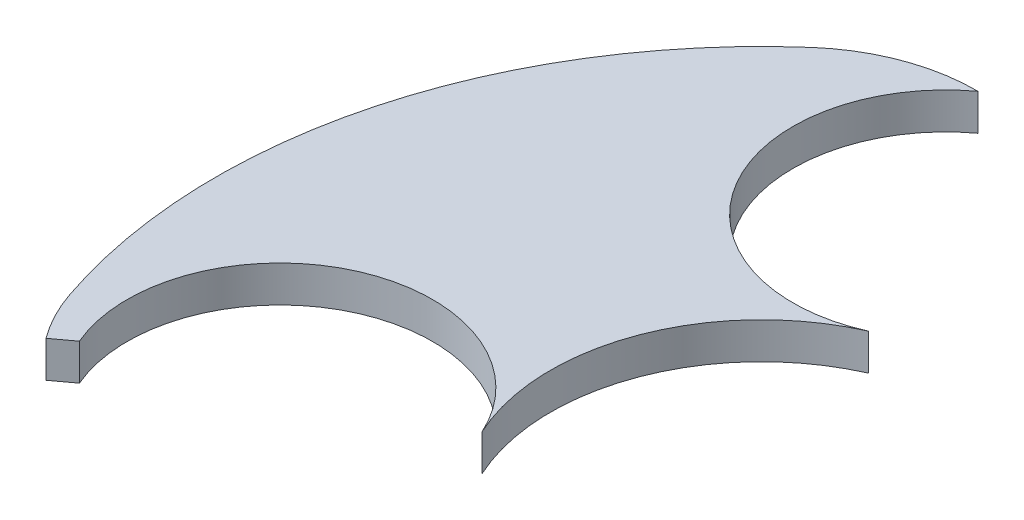
SolidWorks part; units mm, degrees
ref_plane "Plan de face" through (0, 0, 0) normal (0, 0, 1) x (1, 0, 0)
ref_plane "Plan de dessus" through (0, 0, 0) normal (0, 1, 0) x (1, 0, 0)
ref_plane "Plan de droite" through (0, 0, 0) normal (1, 0, 0) x (0, 0, -1)
sketch "Esquisse1" plane through (0, 0, 0) normal (0, 1, 0) x (1, 0, 0)
  line L0 (-84.4585, -44.8337) -> (-81.8158, -42.8843)
  line L3 (-9.4508, 5.6286) -> (-14.9085, -3.5351) construction
  line L5 (3.3105, -15.9387) -> (9.4508, -5.6286) construction
  line L12 (0, 0) -> (-80, 0) construction
  line L13 (-64.3402, -29.9927) -> (-49.9731, 23.6261) construction
  line L14 (-65, 0) -> (-64.3402, -29.9927) construction
  arc A0 (-43.3841, -25.9503) -> (3.3105, -15.9387) centre (-29.8877, 25) ccw construction
  arc A1 (-20.0888, -3.4918) -> (-14.9085, -3.5351) centre (-17.486, -2) ccw construction
  arc A2 (-20.0888, -3.4918) -> (-28.7931, 12.5396) centre (323.3678, 193.369) cw construction
  arc A3 (-14.9569, 14.9816) -> (-23.7434, -42.1488) centre (-16.9847, -13.9474) ccw
  arc A36 (-49.9731, 23.6261) -> (-64.3402, -29.9927) centre (-16.9847, -13.9474) ccw construction
  arc A37 (-66.4673, 42.4128) -> (-88.018, -38.0154) centre (-16.9847, -13.9474) ccw
  arc A40 (-88.018, -38.0154) -> (-84.4585, -44.8337) centre (-64.3402, -29.9927) ccw
  arc A41 (9.4508, -5.6286) -> (-9.4508, 5.6286) centre (0, 0) ccw construction
  arc A42 (-17.0622, 36.0526) -> (-48.1141, -53.0749) centre (-16.9847, -13.9474) ccw construction
  arc A43 (-49.802, 48.6255) -> (-28.7931, 12.5396) centre (-37.3441, 31.7198) ccw
  arc A44 (-49.802, 48.6255) -> (-66.4673, 42.4128) centre (-49.9731, 23.6261) ccw
  arc A45 (-43.3841, -25.9503) -> (-81.8158, -42.8843) centre (-62.5009, -34.6421) ccw
  point P78 (-56.6847, 2.6915)
  point P85 (-65, 0)
  dimension "D4" = 25
  dimension "D5" = 12
  dimension "D6" = 21
  dimension "D7" = 25
  dimension "D8" = 25
  dimension "D10" = 3
  dimension "D11" = 17.6
  dimension "D18" = 80
  dimension "D20" = 75
  dimension "D26" = 11
  dimension "D13" = 50
  dimension "D14" = 21
  dimension "D12" = 2
  dimension "D22" = 30
  dimension "D23" = 75
  dimension "D24" = 28
  dimension "D25" = 15
  dimension "D30" = 15
  dimension "D32" = 5
extrude "Boss.-Extru.1" add sketch "Esquisse1" along normal blind 5 contours A45 A3 A43 A44 A37 A40 L0 region at (-68.3311, 0, -4.6156)
